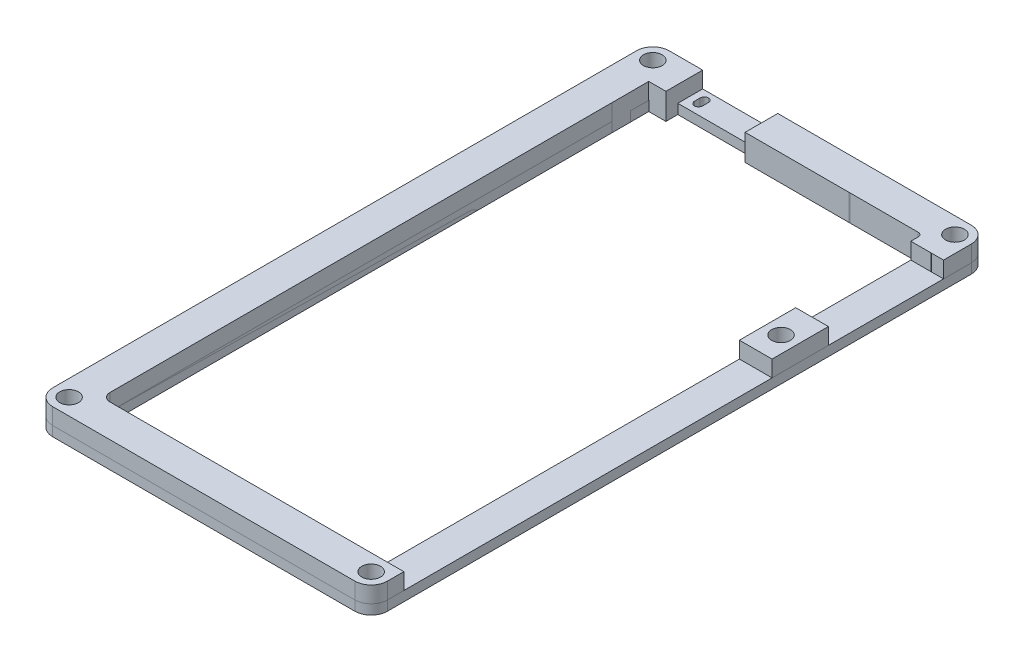
SolidWorks part; units mm, degrees
ref_plane "Front Plane" through (0, 0, 0) normal (0, 0, 1) x (1, 0, 0)
ref_plane "Top Plane" through (0, 0, 0) normal (0, 1, 0) x (1, 0, 0)
ref_plane "Right Plane" through (0, 0, 0) normal (1, 0, 0) x (0, 0, -1)
sketch "partA" plane through (0, 0, 0) normal (0, 1, 0) x (1, 0, 0)
  line L0 (1, 63.5) -> (19.3, 63.5)
  line L1 (19.3, 63.5) -> (22.7142, 66.9142)
  line L2 (0, 62.5) -> (0, 1)
  line L3 (33, 66.1) -> (33, 67)
  line L4 (32.5, 67.5) -> (24.1284, 67.5)
  line L5 (1, 0) -> (37, 0)
  line L6 (-4, -2) -> (-4, 69.5)
  line L7 (-2, 71.5) -> (2.1, 71.5)
  line L8 (37, 0) -> (37, -2)
  line L9 (35, -4) -> (-2, -4)
  line L10 (2.1, 71.5) -> (2.1, 67)
  line L11 (2.6, 66.5) -> (10.8, 66.5)
  line L12 (11.3, 67) -> (11.3, 71.5)
  line L13 (37, 66.1) -> (35.5, 66.1)
  line L14 (35, 65.6) -> (35, 52.5)
  line L15 (35.5, 52) -> (37, 52)
  line L16 (11.3, 71.5) -> (35, 71.5)
  line L17 (37, 69.5) -> (37, 66.1)
  line L18 (37, 45.1) -> (37, 52)
  line L19 (33, 45.1) -> (33, 52)
  line L20 (33, 45.1) -> (37, 45.1)
  line L21 (33, 66.1) -> (33, 52)
  line L22 (37, 52) -> (33, 52)
  line L23 (37, 66.1) -> (33, 66.1)
  arc A0 (19.3, 63.4975) -> (19.3, 63.5025) centre (19.3, 63.5) ccw
  arc A1 (1, 63.5025) -> (1, 63.4975) centre (1, 63.5) ccw
  arc A2 (22.716, 66.9124) -> (22.7124, 66.916) centre (22.7142, 66.9142) ccw
  arc A3 (19.2982, 63.5018) -> (19.3018, 63.4982) centre (19.3, 63.5) ccw
  arc A4 (1, 63.5) -> (0, 62.5) centre (1, 62.5) ccw
  arc A5 (1, 63.4975) -> (1, 63.5025) centre (1, 63.5) ccw
  arc A6 (-0.0025, 62.5) -> (0.0025, 62.5) centre (0, 62.5) ccw
  arc A7 (-0.0025, 1) -> (0.0025, 1) centre (0, 1) ccw
  arc A8 (0.0025, 62.5) -> (-0.0025, 62.5) centre (0, 62.5) ccw
  arc A9 (24.1284, 67.5) -> (22.7142, 66.9142) centre (24.1285, 65.4999) ccw
  arc A10 (24.1284, 67.4975) -> (24.1284, 67.5025) centre (24.1284, 67.5) ccw
  arc A11 (22.7124, 66.916) -> (22.716, 66.9124) centre (22.7142, 66.9142) ccw
  arc A12 (33.0025, 67) -> (32.9975, 67) centre (33, 67) ccw
  arc A13 (32.9975, 66.1) -> (33.0025, 66.1) centre (33, 66.1) ccw
  arc A14 (33, 67) -> (32.5, 67.5) centre (32.5, 67) ccw
  arc A15 (32.9975, 67) -> (33.0025, 67) centre (33, 67) ccw
  arc A16 (32.5, 67.5025) -> (32.5, 67.4975) centre (32.5, 67.5) ccw
  arc A17 (24.1284, 67.5025) -> (24.1284, 67.4975) centre (24.1284, 67.5) ccw
  arc A18 (32.5, 67.4975) -> (32.5, 67.5025) centre (32.5, 67.5) ccw
  arc A19 (0, 1) -> (1, 0) centre (1, 1) ccw
  arc A20 (0.0025, 1) -> (-0.0025, 1) centre (0, 1) ccw
  arc A21 (1, -0.0025) -> (1, 0.0025) centre (1, 0) ccw
  arc A22 (37, -0.0025) -> (37, 0.0025) centre (37, 0) ccw
  arc A23 (1, 0.0025) -> (1, -0.0025) centre (1, 0) ccw
  arc A24 (-3.9975, 69.5) -> (-4.0025, 69.5) centre (-4, 69.5) ccw
  arc A25 (-4.0025, -2) -> (-3.9975, -2) centre (-4, -2) ccw
  arc A26 (-2, 71.5) -> (-4, 69.5) centre (-2, 69.5) ccw
  arc A27 (-2, 71.4975) -> (-2, 71.5025) centre (-2, 71.5) ccw
  arc A28 (-4.0025, 69.5) -> (-3.9975, 69.5) centre (-4, 69.5) ccw
  arc A29 (2.1, 71.4975) -> (2.1, 71.5025) centre (2.1, 71.5) ccw
  arc A30 (-2, 71.5025) -> (-2, 71.4975) centre (-2, 71.5) ccw
  arc A31 (36.9975, -2) -> (37.0025, -2) centre (37, -2) ccw
  arc A32 (37.0025, 0) -> (36.9975, 0) centre (37, 0) ccw
  arc A33 (35, -4) -> (37, -2) centre (35, -2) ccw
  arc A34 (35, -3.9975) -> (35, -4.0025) centre (35, -4) ccw
  arc A35 (37.0025, -2) -> (36.9975, -2) centre (37, -2) ccw
  arc A36 (-2, -3.9975) -> (-2, -4.0025) centre (-2, -4) ccw
  arc A37 (35, -4.0025) -> (35, -3.9975) centre (35, -4) ccw
  arc A38 (-4, -2) -> (-2, -4) centre (-2, -2) ccw
  arc A39 (-3.9975, -2) -> (-4.0025, -2) centre (-4, -2) ccw
  arc A40 (-2, -4.0025) -> (-2, -3.9975) centre (-2, -4) ccw
  arc A41 (2.0975, 67) -> (2.1025, 67) centre (2.1, 67) ccw
  arc A42 (2.1025, 71.5) -> (2.0975, 71.5) centre (2.1, 71.5) ccw
  arc A43 (2.1, 67) -> (2.6, 66.5) centre (2.6, 67) ccw
  arc A44 (2.1025, 67) -> (2.0975, 67) centre (2.1, 67) ccw
  arc A45 (2.6, 66.4975) -> (2.6, 66.5025) centre (2.6, 66.5) ccw
  arc A46 (10.8, 66.4975) -> (10.8, 66.5025) centre (10.8, 66.5) ccw
  arc A47 (2.6, 66.5025) -> (2.6, 66.4975) centre (2.6, 66.5) ccw
  arc A48 (10.8, 66.5) -> (11.3, 67) centre (10.8, 67) ccw
  arc A49 (10.8, 66.5025) -> (10.8, 66.4975) centre (10.8, 66.5) ccw
  arc A50 (11.3025, 67) -> (11.2975, 67) centre (11.3, 67) ccw
  arc A51 (11.3025, 71.5) -> (11.2975, 71.5) centre (11.3, 71.5) ccw
  arc A52 (11.2975, 67) -> (11.3025, 67) centre (11.3, 67) ccw
  arc A53 (35.5, 66.1025) -> (35.5, 66.0975) centre (35.5, 66.1) ccw
  arc A54 (37, 66.0975) -> (37, 66.1025) centre (37, 66.1) ccw
  arc A55 (35.5, 66.1) -> (35, 65.6) centre (35.5, 65.6) ccw
  arc A56 (35.5, 66.0975) -> (35.5, 66.1025) centre (35.5, 66.1) ccw
  arc A57 (34.9975, 65.6) -> (35.0025, 65.6) centre (35, 65.6) ccw
  arc A58 (34.9975, 52.5) -> (35.0025, 52.5) centre (35, 52.5) ccw
  arc A59 (35.0025, 65.6) -> (34.9975, 65.6) centre (35, 65.6) ccw
  arc A60 (35, 52.5) -> (35.5, 52) centre (35.5, 52.5) ccw
  arc A61 (35.0025, 52.5) -> (34.9975, 52.5) centre (35, 52.5) ccw
  arc A62 (35.5, 51.9975) -> (35.5, 52.0025) centre (35.5, 52) ccw
  arc A63 (37, 51.9975) -> (37, 52.0025) centre (37, 52) ccw
  arc A64 (35.5, 52.0025) -> (35.5, 51.9975) centre (35.5, 52) ccw
  arc A65 (35, 71.4975) -> (35, 71.5025) centre (35, 71.5) ccw
  arc A66 (11.3, 71.5025) -> (11.3, 71.4975) centre (11.3, 71.5) ccw
  arc A67 (37, 69.5) -> (35, 71.5) centre (35, 69.5) ccw
  arc A68 (36.9975, 69.5) -> (37.0025, 69.5) centre (37, 69.5) ccw
  arc A69 (35, 71.5025) -> (35, 71.4975) centre (35, 71.5) ccw
  arc A70 (36.9975, 66.1) -> (37.0025, 66.1) centre (37, 66.1) ccw
  arc A71 (37.0025, 69.5) -> (36.9975, 69.5) centre (37, 69.5) ccw
  arc A72 (37.0025, 52) -> (36.9975, 52) centre (37, 52) ccw
  arc A73 (36.9975, 45.1) -> (37.0025, 45.1) centre (37, 45.1) ccw
  arc A74 (33.0025, 52) -> (32.9975, 52) centre (33, 52) ccw
  arc A75 (32.9975, 45.1) -> (33.0025, 45.1) centre (33, 45.1) ccw
  arc A76 (37, 45.0975) -> (37, 45.1025) centre (37, 45.1) ccw
  arc A77 (33, 45.1025) -> (33, 45.0975) centre (33, 45.1) ccw
  arc A78 (32.9975, 52) -> (33.0025, 52) centre (33, 52) ccw
  arc A79 (33.0025, 66.1) -> (32.9975, 66.1) centre (33, 66.1) ccw
  arc A80 (33, 52.0025) -> (33, 51.9975) centre (33, 52) ccw
  arc A81 (37, 51.9975) -> (37, 52.0025) centre (37, 52) ccw
  arc A82 (33, 66.1025) -> (33, 66.0975) centre (33, 66.1) ccw
  arc A83 (37, 66.0975) -> (37, 66.1025) centre (37, 66.1) ccw
  circle A84 centre (-2, 69.5) radius 1
  circle A85 centre (35, 69.5) radius 1
  circle A86 centre (35, -2) radius 1
  circle A87 centre (-2, -2) radius 1
  circle A88 centre (35, 48.2) radius 1
  circle A89 centre (33.3, 51.7) radius 0.3
  circle A90 centre (34.1, 51.7) radius 0.3
  circle A91 centre (34.9, 51.7) radius 0.3
  circle A92 centre (35.7, 51.7) radius 0.3
  circle A93 centre (33.3, 66.4) radius 0.3
  circle A94 centre (34.1, 66.4) radius 0.3
  circle A95 centre (34.9, 66.4) radius 0.3
  circle A96 centre (35.7, 66.4) radius 0.3
sketch "partC" plane through (0, 0, 0) normal (0, 1, 0) x (1, 0, 0)
  line L0 (-4, -2) -> (-4, 69.5)
  line L1 (-2, 71.5) -> (35, 71.5)
  line L2 (37, 69.5) -> (37, -2)
  line L3 (35, -4) -> (-2, -4)
  line L4 (-4, -2) -> (-4, 69.5)
  line L5 (-2, 71.5) -> (35, 71.5)
  line L6 (37, 69.5) -> (37, -2)
  line L7 (35, -4) -> (-2, -4)
  line L8 (2.9, 69.7) -> (2.9, 70.4)
  line L9 (3.9, 70.4) -> (3.9, 69.7)
  line L10 (9.5, 69.7) -> (9.5, 70.4)
  line L11 (10.5, 70.4) -> (10.5, 69.7)
  line L12 (29, 68) -> (23.5, 68)
  line L13 (23, 67.5) -> (23, 50.5)
  line L14 (23.5, 50) -> (29, 50)
  line L15 (29.5, 50.5) -> (29.5, 67.5)
  line L16 (20.7, 1.7) -> (20.7, 2.6)
  line L17 (21.2, 3.1) -> (29.8, 3.1)
  line L18 (30.3, 2.6) -> (30.3, 1.7)
  line L19 (29.8, 1.2) -> (21.2, 1.2)
  line L20 (12.6, 15.2) -> (12.6, 16.1)
  line L21 (13.1, 16.6) -> (21.7, 16.6)
  line L22 (22.2, 16.1) -> (22.2, 15.2)
  line L23 (21.7, 14.7) -> (13.1, 14.7)
  line L24 (20.7, 19.7) -> (20.7, 20.6)
  line L25 (21.2, 21.1) -> (29.8, 21.1)
  line L26 (30.3, 20.6) -> (30.3, 19.7)
  line L27 (29.8, 19.2) -> (21.2, 19.2)
  line L28 (12.6, 33.2) -> (12.6, 34.1)
  line L29 (13.1, 34.6) -> (21.7, 34.6)
  line L30 (22.2, 34.1) -> (22.2, 33.2)
  line L31 (21.7, 32.7) -> (13.1, 32.7)
  arc A0 (-3.9975, 69.5) -> (-4.0025, 69.5) centre (-4, 69.5) ccw
  arc A1 (-4.0025, -2) -> (-3.9975, -2) centre (-4, -2) ccw
  arc A2 (-2, 71.5) -> (-4, 69.5) centre (-2, 69.5) ccw
  arc A3 (-2, 71.4975) -> (-2, 71.5025) centre (-2, 71.5) ccw
  arc A4 (-4.0025, 69.5) -> (-3.9975, 69.5) centre (-4, 69.5) ccw
  arc A5 (35, 71.4975) -> (35, 71.5025) centre (35, 71.5) ccw
  arc A6 (-2, 71.5025) -> (-2, 71.4975) centre (-2, 71.5) ccw
  arc A7 (-4, -2) -> (-2, -4) centre (-2, -2) ccw
  arc A8 (-3.9975, -2) -> (-4.0025, -2) centre (-4, -2) ccw
  arc A9 (-2, -4.0025) -> (-2, -3.9975) centre (-2, -4) ccw
  arc A10 (37, 69.5) -> (35, 71.5) centre (35, 69.5) ccw
  arc A11 (36.9975, 69.5) -> (37.0025, 69.5) centre (37, 69.5) ccw
  arc A12 (35, 71.5025) -> (35, 71.4975) centre (35, 71.5) ccw
  arc A13 (36.9975, -2) -> (37.0025, -2) centre (37, -2) ccw
  arc A14 (37.0025, 69.5) -> (36.9975, 69.5) centre (37, 69.5) ccw
  arc A15 (35, -4) -> (37, -2) centre (35, -2) ccw
  arc A16 (35, -3.9975) -> (35, -4.0025) centre (35, -4) ccw
  arc A17 (37.0025, -2) -> (36.9975, -2) centre (37, -2) ccw
  arc A18 (-2, -3.9975) -> (-2, -4.0025) centre (-2, -4) ccw
  arc A19 (35, -4.0025) -> (35, -3.9975) centre (35, -4) ccw
  arc A20 (-3.9975, 69.5) -> (-4.0025, 69.5) centre (-4, 69.5) ccw
  arc A21 (-4.0025, -2) -> (-3.9975, -2) centre (-4, -2) ccw
  arc A22 (-2, 71.5) -> (-4, 69.5) centre (-2, 69.5) ccw
  arc A23 (-2, 71.4975) -> (-2, 71.5025) centre (-2, 71.5) ccw
  arc A24 (-4.0025, 69.5) -> (-3.9975, 69.5) centre (-4, 69.5) ccw
  arc A25 (35, 71.4975) -> (35, 71.5025) centre (35, 71.5) ccw
  arc A26 (-2, 71.5025) -> (-2, 71.4975) centre (-2, 71.5) ccw
  arc A27 (-4, -2) -> (-2, -4) centre (-2, -2) ccw
  arc A28 (-3.9975, -2) -> (-4.0025, -2) centre (-4, -2) ccw
  arc A29 (-2, -4.0025) -> (-2, -3.9975) centre (-2, -4) ccw
  arc A30 (37, 69.5) -> (35, 71.5) centre (35, 69.5) ccw
  arc A31 (36.9975, 69.5) -> (37.0025, 69.5) centre (37, 69.5) ccw
  arc A32 (35, 71.5025) -> (35, 71.4975) centre (35, 71.5) ccw
  arc A33 (36.9975, -2) -> (37.0025, -2) centre (37, -2) ccw
  arc A34 (37.0025, 69.5) -> (36.9975, 69.5) centre (37, 69.5) ccw
  arc A35 (35, -4) -> (37, -2) centre (35, -2) ccw
  arc A36 (35, -3.9975) -> (35, -4.0025) centre (35, -4) ccw
  arc A37 (37.0025, -2) -> (36.9975, -2) centre (37, -2) ccw
  arc A38 (-2, -3.9975) -> (-2, -4.0025) centre (-2, -4) ccw
  arc A39 (35, -4.0025) -> (35, -3.9975) centre (35, -4) ccw
  arc A40 (2.9025, 70.4) -> (2.8975, 70.4) centre (2.9, 70.4) ccw
  arc A41 (2.8975, 69.7) -> (2.9025, 69.7) centre (2.9, 69.7) ccw
  arc A42 (3.4, 70.9) -> (2.9, 70.4) centre (3.4, 70.4) ccw
  arc A43 (3.4, 70.8975) -> (3.4, 70.9025) centre (3.4, 70.9) ccw
  arc A44 (2.8975, 70.4) -> (2.9025, 70.4) centre (2.9, 70.4) ccw
  arc A45 (3.9, 70.4) -> (3.4, 70.9) centre (3.4, 70.4) ccw
  arc A46 (3.8975, 70.4) -> (3.9025, 70.4) centre (3.9, 70.4) ccw
  arc A47 (3.4, 70.9025) -> (3.4, 70.8975) centre (3.4, 70.9) ccw
  arc A48 (3.8975, 69.7) -> (3.9025, 69.7) centre (3.9, 69.7) ccw
  arc A49 (3.9025, 70.4) -> (3.8975, 70.4) centre (3.9, 70.4) ccw
  arc A50 (3.4, 69.2) -> (3.9, 69.7) centre (3.4, 69.7) ccw
  arc A51 (3.4, 69.2025) -> (3.4, 69.1975) centre (3.4, 69.2) ccw
  arc A52 (3.9025, 69.7) -> (3.8975, 69.7) centre (3.9, 69.7) ccw
  arc A53 (2.9, 69.7) -> (3.4, 69.2) centre (3.4, 69.7) ccw
  arc A54 (2.9025, 69.7) -> (2.8975, 69.7) centre (2.9, 69.7) ccw
  arc A55 (3.4, 69.1975) -> (3.4, 69.2025) centre (3.4, 69.2) ccw
  arc A56 (9.5025, 70.4) -> (9.4975, 70.4) centre (9.5, 70.4) ccw
  arc A57 (9.4975, 69.7) -> (9.5025, 69.7) centre (9.5, 69.7) ccw
  arc A58 (10, 70.9) -> (9.5, 70.4) centre (10, 70.4) ccw
  arc A59 (10, 70.8975) -> (10, 70.9025) centre (10, 70.9) ccw
  arc A60 (9.4975, 70.4) -> (9.5025, 70.4) centre (9.5, 70.4) ccw
  arc A61 (10.5, 70.4) -> (10, 70.9) centre (10, 70.4) ccw
  arc A62 (10.4975, 70.4) -> (10.5025, 70.4) centre (10.5, 70.4) ccw
  arc A63 (10, 70.9025) -> (10, 70.8975) centre (10, 70.9) ccw
  arc A64 (10.4975, 69.7) -> (10.5025, 69.7) centre (10.5, 69.7) ccw
  arc A65 (10.5025, 70.4) -> (10.4975, 70.4) centre (10.5, 70.4) ccw
  arc A66 (10, 69.2) -> (10.5, 69.7) centre (10, 69.7) ccw
  arc A67 (10, 69.2025) -> (10, 69.1975) centre (10, 69.2) ccw
  arc A68 (10.5025, 69.7) -> (10.4975, 69.7) centre (10.5, 69.7) ccw
  arc A69 (9.5, 69.7) -> (10, 69.2) centre (10, 69.7) ccw
  arc A70 (9.5025, 69.7) -> (9.4975, 69.7) centre (9.5, 69.7) ccw
  arc A71 (10, 69.1975) -> (10, 69.2025) centre (10, 69.2) ccw
  arc A72 (23.5, 68.0025) -> (23.5, 67.9975) centre (23.5, 68) ccw
  arc A73 (29, 67.9975) -> (29, 68.0025) centre (29, 68) ccw
  arc A74 (23.5, 68) -> (23, 67.5) centre (23.5, 67.5) ccw
  arc A75 (23.5, 67.9975) -> (23.5, 68.0025) centre (23.5, 68) ccw
  arc A76 (22.9975, 67.5) -> (23.0025, 67.5) centre (23, 67.5) ccw
  arc A77 (22.9975, 50.5) -> (23.0025, 50.5) centre (23, 50.5) ccw
  arc A78 (23.0025, 67.5) -> (22.9975, 67.5) centre (23, 67.5) ccw
  arc A79 (23, 50.5) -> (23.5, 50) centre (23.5, 50.5) ccw
  arc A80 (23.0025, 50.5) -> (22.9975, 50.5) centre (23, 50.5) ccw
  arc A81 (23.5, 49.9975) -> (23.5, 50.0025) centre (23.5, 50) ccw
  arc A82 (29, 49.9975) -> (29, 50.0025) centre (29, 50) ccw
  arc A83 (23.5, 50.0025) -> (23.5, 49.9975) centre (23.5, 50) ccw
  arc A84 (29, 50) -> (29.5, 50.5) centre (29, 50.5) ccw
  arc A85 (29, 50.0025) -> (29, 49.9975) centre (29, 50) ccw
  arc A86 (29.5025, 50.5) -> (29.4975, 50.5) centre (29.5, 50.5) ccw
  arc A87 (29.5025, 67.5) -> (29.4975, 67.5) centre (29.5, 67.5) ccw
  arc A88 (29.4975, 50.5) -> (29.5025, 50.5) centre (29.5, 50.5) ccw
  arc A89 (29.5, 67.5) -> (29, 68) centre (29, 67.5) ccw
  arc A90 (29.4975, 67.5) -> (29.5025, 67.5) centre (29.5, 67.5) ccw
  arc A91 (29, 68.0025) -> (29, 67.9975) centre (29, 68) ccw
  arc A92 (20.7025, 2.6) -> (20.6975, 2.6) centre (20.7, 2.6) ccw
  arc A93 (20.6975, 1.7) -> (20.7025, 1.7) centre (20.7, 1.7) ccw
  arc A94 (21.2, 3.1) -> (20.7, 2.6) centre (21.2, 2.6) ccw
  arc A95 (21.2, 3.0975) -> (21.2, 3.1025) centre (21.2, 3.1) ccw
  arc A96 (20.6975, 2.6) -> (20.7025, 2.6) centre (20.7, 2.6) ccw
  arc A97 (29.8, 3.0975) -> (29.8, 3.1025) centre (29.8, 3.1) ccw
  arc A98 (21.2, 3.1025) -> (21.2, 3.0975) centre (21.2, 3.1) ccw
  arc A99 (30.3, 2.6) -> (29.8, 3.1) centre (29.8, 2.6) ccw
  arc A100 (30.2975, 2.6) -> (30.3025, 2.6) centre (30.3, 2.6) ccw
  arc A101 (29.8, 3.1025) -> (29.8, 3.0975) centre (29.8, 3.1) ccw
  arc A102 (30.2975, 1.7) -> (30.3025, 1.7) centre (30.3, 1.7) ccw
  arc A103 (30.3025, 2.6) -> (30.2975, 2.6) centre (30.3, 2.6) ccw
  arc A104 (29.8, 1.2) -> (30.3, 1.7) centre (29.8, 1.7) ccw
  arc A105 (29.8, 1.2025) -> (29.8, 1.1975) centre (29.8, 1.2) ccw
  arc A106 (30.3025, 1.7) -> (30.2975, 1.7) centre (30.3, 1.7) ccw
  arc A107 (21.2, 1.2025) -> (21.2, 1.1975) centre (21.2, 1.2) ccw
  arc A108 (29.8, 1.1975) -> (29.8, 1.2025) centre (29.8, 1.2) ccw
  arc A109 (20.7, 1.7) -> (21.2, 1.2) centre (21.2, 1.7) ccw
  arc A110 (20.7025, 1.7) -> (20.6975, 1.7) centre (20.7, 1.7) ccw
  arc A111 (21.2, 1.1975) -> (21.2, 1.2025) centre (21.2, 1.2) ccw
  arc A112 (12.6025, 16.1) -> (12.5975, 16.1) centre (12.6, 16.1) ccw
  arc A113 (12.5975, 15.2) -> (12.6025, 15.2) centre (12.6, 15.2) ccw
  arc A114 (13.1, 16.6) -> (12.6, 16.1) centre (13.1, 16.1) ccw
  arc A115 (13.1, 16.5975) -> (13.1, 16.6025) centre (13.1, 16.6) ccw
  arc A116 (12.5975, 16.1) -> (12.6025, 16.1) centre (12.6, 16.1) ccw
  arc A117 (21.7, 16.5975) -> (21.7, 16.6025) centre (21.7, 16.6) ccw
  arc A118 (13.1, 16.6025) -> (13.1, 16.5975) centre (13.1, 16.6) ccw
  arc A119 (22.2, 16.1) -> (21.7, 16.6) centre (21.7, 16.1) ccw
  arc A120 (22.1975, 16.1) -> (22.2025, 16.1) centre (22.2, 16.1) ccw
  arc A121 (21.7, 16.6025) -> (21.7, 16.5975) centre (21.7, 16.6) ccw
  arc A122 (22.1975, 15.2) -> (22.2025, 15.2) centre (22.2, 15.2) ccw
  arc A123 (22.2025, 16.1) -> (22.1975, 16.1) centre (22.2, 16.1) ccw
  arc A124 (21.7, 14.7) -> (22.2, 15.2) centre (21.7, 15.2) ccw
  arc A125 (21.7, 14.7025) -> (21.7, 14.6975) centre (21.7, 14.7) ccw
  arc A126 (22.2025, 15.2) -> (22.1975, 15.2) centre (22.2, 15.2) ccw
  arc A127 (13.1, 14.7025) -> (13.1, 14.6975) centre (13.1, 14.7) ccw
  arc A128 (21.7, 14.6975) -> (21.7, 14.7025) centre (21.7, 14.7) ccw
  arc A129 (12.6, 15.2) -> (13.1, 14.7) centre (13.1, 15.2) ccw
  arc A130 (12.6025, 15.2) -> (12.5975, 15.2) centre (12.6, 15.2) ccw
  arc A131 (13.1, 14.6975) -> (13.1, 14.7025) centre (13.1, 14.7) ccw
  arc A132 (20.7025, 20.6) -> (20.6975, 20.6) centre (20.7, 20.6) ccw
  arc A133 (20.6975, 19.7) -> (20.7025, 19.7) centre (20.7, 19.7) ccw
  arc A134 (21.2, 21.1) -> (20.7, 20.6) centre (21.2, 20.6) ccw
  arc A135 (21.2, 21.0975) -> (21.2, 21.1025) centre (21.2, 21.1) ccw
  arc A136 (20.6975, 20.6) -> (20.7025, 20.6) centre (20.7, 20.6) ccw
  arc A137 (29.8, 21.0975) -> (29.8, 21.1025) centre (29.8, 21.1) ccw
  arc A138 (21.2, 21.1025) -> (21.2, 21.0975) centre (21.2, 21.1) ccw
  arc A139 (30.3, 20.6) -> (29.8, 21.1) centre (29.8, 20.6) ccw
  arc A140 (30.2975, 20.6) -> (30.3025, 20.6) centre (30.3, 20.6) ccw
  arc A141 (29.8, 21.1025) -> (29.8, 21.0975) centre (29.8, 21.1) ccw
  arc A142 (30.2975, 19.7) -> (30.3025, 19.7) centre (30.3, 19.7) ccw
  arc A143 (30.3025, 20.6) -> (30.2975, 20.6) centre (30.3, 20.6) ccw
  arc A144 (29.8, 19.2) -> (30.3, 19.7) centre (29.8, 19.7) ccw
  arc A145 (29.8, 19.2025) -> (29.8, 19.1975) centre (29.8, 19.2) ccw
  arc A146 (30.3025, 19.7) -> (30.2975, 19.7) centre (30.3, 19.7) ccw
  arc A147 (21.2, 19.2025) -> (21.2, 19.1975) centre (21.2, 19.2) ccw
  arc A148 (29.8, 19.1975) -> (29.8, 19.2025) centre (29.8, 19.2) ccw
  arc A149 (20.7, 19.7) -> (21.2, 19.2) centre (21.2, 19.7) ccw
  arc A150 (20.7025, 19.7) -> (20.6975, 19.7) centre (20.7, 19.7) ccw
  arc A151 (21.2, 19.1975) -> (21.2, 19.2025) centre (21.2, 19.2) ccw
  arc A152 (12.6025, 34.1) -> (12.5975, 34.1) centre (12.6, 34.1) ccw
  arc A153 (12.5975, 33.2) -> (12.6025, 33.2) centre (12.6, 33.2) ccw
  arc A154 (13.1, 34.6) -> (12.6, 34.1) centre (13.1, 34.1) ccw
  arc A155 (13.1, 34.5975) -> (13.1, 34.6025) centre (13.1, 34.6) ccw
  arc A156 (12.5975, 34.1) -> (12.6025, 34.1) centre (12.6, 34.1) ccw
  arc A157 (21.7, 34.5975) -> (21.7, 34.6025) centre (21.7, 34.6) ccw
  arc A158 (13.1, 34.6025) -> (13.1, 34.5975) centre (13.1, 34.6) ccw
  arc A159 (22.2, 34.1) -> (21.7, 34.6) centre (21.7, 34.1) ccw
  arc A160 (22.1975, 34.1) -> (22.2025, 34.1) centre (22.2, 34.1) ccw
  arc A161 (21.7, 34.6025) -> (21.7, 34.5975) centre (21.7, 34.6) ccw
  arc A162 (22.1975, 33.2) -> (22.2025, 33.2) centre (22.2, 33.2) ccw
  arc A163 (22.2025, 34.1) -> (22.1975, 34.1) centre (22.2, 34.1) ccw
  arc A164 (21.7, 32.7) -> (22.2, 33.2) centre (21.7, 33.2) ccw
  arc A165 (21.7, 32.7025) -> (21.7, 32.6975) centre (21.7, 32.7) ccw
  arc A166 (22.2025, 33.2) -> (22.1975, 33.2) centre (22.2, 33.2) ccw
  arc A167 (13.1, 32.7025) -> (13.1, 32.6975) centre (13.1, 32.7) ccw
  arc A168 (21.7, 32.6975) -> (21.7, 32.7025) centre (21.7, 32.7) ccw
  arc A169 (12.6, 33.2) -> (13.1, 32.7) centre (13.1, 33.2) ccw
  arc A170 (12.6025, 33.2) -> (12.5975, 33.2) centre (12.6, 33.2) ccw
  arc A171 (13.1, 32.6975) -> (13.1, 32.7025) centre (13.1, 32.7) ccw
  circle A172 centre (-2, 69.5) radius 1
  circle A173 centre (35, 69.5) radius 1
  circle A174 centre (35, -2) radius 1
  circle A175 centre (-2, -2) radius 1
  circle A176 centre (35, 48.2) radius 1
sketch "A-modify" plane through (0, 0, 0) normal (0, 1, 0) x (1, 0, 0)
  line L0 (1, 63.5) -> (1.0025, 63.5)
  line L1 (35, 52.5025) -> (35, 52.5)
  line L2 (0, 62.5) -> (0, 1)
  line L3 (33, 66.1) -> (33, 67)
  line L4 (32.5, 67.5) -> (24.1284, 67.5)
  line L5 (1, 0) -> (37, 0)
  line L6 (-4, -2) -> (-4, 69.5)
  line L7 (-2, 71.5) -> (2.1, 71.5)
  line L8 (37, 0) -> (37, -2)
  line L9 (35, -4) -> (-2, -4)
  line L10 (2.1, 71.5) -> (2.1, 67)
  line L11 (2.6, 66.5) -> (2.6025, 66.5)
  line L12 (11.3, 67) -> (11.3, 67.0025)
  line L13 (37, 66.1) -> (35.5, 66.1)
  line L14 (35, 65.6) -> (35, 65.5975)
  line L15 (35.5, 52) -> (37, 52)
  line L16 (11.3, 71.5) -> (35, 71.5)
  line L17 (37, 69.5) -> (37, 66.1)
  line L18 (37, 45.1) -> (37, 52)
  line L19 (33, 45.1) -> (33, 52)
  line L20 (33, 45.1) -> (37, 45.1)
  line L21 (33, 66.1) -> (33, 66.0975)
  line L22 (37, 52) -> (35.4975, 52)
  line L23 (37, 66.1) -> (35.4975, 66.1)
  line L24 (-0.0025, 67) -> (0.0025, 62.5)
  line L25 (19.2975, 63.5) -> (19.3, 63.5)
  line L27 (24.1284, 67.4975) -> (11.3, 67.4975)
  line L28 (33, 52.0025) -> (33, 52)
  line L29 (33.0025, 52) -> (33, 52)
  line L30 (33, 51.9975) -> (35.5, 51.9975)
  line L31 (33.0025, 66.1) -> (33, 66.1)
  line L32 (35.5, 66.0975) -> (33, 66.0975)
  line L33 (10.7975, 66.5) -> (10.8, 66.5)
  line L34 (11.3, 67.4975) -> (11.3, 71.5)
  line L35 (2.0975, 67) -> (-0.0025, 67)
  arc A0 (19.3, 63.4975) -> (19.3, 63.5025) centre (19.3, 63.5) ccw
  arc A1 (1, 63.5025) -> (1, 63.4975) centre (1, 63.5) ccw
  arc A2 (22.716, 66.9124) -> (22.7124, 66.916) centre (22.7142, 66.9142) ccw
  arc A3 (19.2982, 63.5018) -> (19.3018, 63.4982) centre (19.3, 63.5) ccw
  arc A4 (1, 63.5) -> (0.9975, 63.5) centre (1, 62.5) ccw
  arc A5 (1, 63.4975) -> (1, 63.5025) centre (1, 63.5) ccw
  arc A6 (-0.0025, 62.5) -> (0.0025, 62.5) centre (0, 62.5) ccw
  arc A7 (-0.0025, 1) -> (0.0025, 1) centre (0, 1) ccw
  arc A8 (0.0025, 62.5) -> (-0.0025, 62.5) centre (0, 62.5) ccw
  arc A9 (24.1284, 67.5) -> (24.0285, 67.4975) centre (24.1285, 65.4999) ccw
  arc A10 (24.1284, 67.4975) -> (24.1284, 67.5025) centre (24.1284, 67.5) ccw
  arc A11 (22.7124, 66.916) -> (22.716, 66.9124) centre (22.7142, 66.9142) ccw
  arc A12 (33.0025, 67) -> (32.9975, 67) centre (33, 67) ccw
  arc A13 (32.9975, 66.1) -> (33.0025, 66.1) centre (33, 66.1) ccw
  arc A14 (33, 67) -> (32.5, 67.5) centre (32.5, 67) ccw
  arc A15 (32.9975, 67) -> (33.0025, 67) centre (33, 67) ccw
  arc A16 (32.5, 67.5025) -> (32.5, 67.4975) centre (32.5, 67.5) ccw
  arc A17 (24.1284, 67.5025) -> (24.1284, 67.4975) centre (24.1284, 67.5) ccw
  arc A18 (32.5, 67.4975) -> (32.5, 67.5025) centre (32.5, 67.5) ccw
  arc A19 (0, 1) -> (1, 0) centre (1, 1) ccw
  arc A20 (0.0025, 1) -> (-0.0025, 1) centre (0, 1) ccw
  arc A21 (1, -0.0025) -> (1, 0.0025) centre (1, 0) ccw
  arc A22 (37, -0.0025) -> (37, 0.0025) centre (37, 0) ccw
  arc A23 (1, 0.0025) -> (1, -0.0025) centre (1, 0) ccw
  arc A24 (-3.9975, 69.5) -> (-4.0025, 69.5) centre (-4, 69.5) ccw
  arc A25 (-4.0025, -2) -> (-3.9975, -2) centre (-4, -2) ccw
  arc A26 (-2, 71.5) -> (-4, 69.5) centre (-2, 69.5) ccw
  arc A27 (-2, 71.4975) -> (-2, 71.5025) centre (-2, 71.5) ccw
  arc A28 (-4.0025, 69.5) -> (-3.9975, 69.5) centre (-4, 69.5) ccw
  arc A29 (2.1, 71.4975) -> (2.1, 71.5025) centre (2.1, 71.5) ccw
  arc A30 (-2, 71.5025) -> (-2, 71.4975) centre (-2, 71.5) ccw
  arc A31 (36.9975, -2) -> (37.0025, -2) centre (37, -2) ccw
  arc A32 (37.0025, 0) -> (36.9975, 0) centre (37, 0) ccw
  arc A33 (35, -4) -> (37, -2) centre (35, -2) ccw
  arc A34 (35, -3.9975) -> (35, -4.0025) centre (35, -4) ccw
  arc A35 (37.0025, -2) -> (36.9975, -2) centre (37, -2) ccw
  arc A36 (-2, -3.9975) -> (-2, -4.0025) centre (-2, -4) ccw
  arc A37 (35, -4.0025) -> (35, -3.9975) centre (35, -4) ccw
  arc A38 (-4, -2) -> (-2, -4) centre (-2, -2) ccw
  arc A39 (-3.9975, -2) -> (-4.0025, -2) centre (-4, -2) ccw
  arc A40 (-2, -4.0025) -> (-2, -3.9975) centre (-2, -4) ccw
  arc A41 (2.0975, 67) -> (2.1025, 67) centre (2.1, 67) ccw
  arc A42 (2.1025, 71.5) -> (2.0975, 71.5) centre (2.1, 71.5) ccw
  circle A43 centre (-2, -2) radius 1.15
  arc A44 (2.1025, 67) -> (2.0975, 67) centre (2.1, 67) ccw
  arc A45 (2.6, 66.4975) -> (2.6, 66.5025) centre (2.6, 66.5) ccw
  arc A46 (10.8, 66.4975) -> (10.8, 66.5025) centre (10.8, 66.5) ccw
  arc A47 (2.6, 66.5025) -> (2.6, 66.4975) centre (2.6, 66.5) ccw
  arc A48 (10.8, 66.5) -> (10.8025, 66.5) centre (10.8, 67) ccw
  arc A49 (10.8, 66.5025) -> (10.8, 66.4975) centre (10.8, 66.5) ccw
  arc A50 (11.3025, 67) -> (11.2975, 67) centre (11.3, 67) ccw
  arc A51 (11.3025, 71.5) -> (11.2975, 71.5) centre (11.3, 71.5) ccw
  arc A52 (11.2975, 67) -> (11.3025, 67) centre (11.3, 67) ccw
  arc A53 (35.5, 66.1025) -> (35.5, 66.0975) centre (35.5, 66.1) ccw
  arc A54 (37, 66.0975) -> (37, 66.1025) centre (37, 66.1) ccw
  arc A55 (35.5, 66.1) -> (35.4975, 66.1) centre (35.5, 65.6) ccw
  arc A56 (35.5, 66.0975) -> (35.5, 66.1025) centre (35.5, 66.1) ccw
  arc A57 (34.9975, 65.6) -> (35.0025, 65.6) centre (35, 65.6) ccw
  arc A58 (34.9975, 52.5) -> (35.0025, 52.5) centre (35, 52.5) ccw
  arc A59 (35.0025, 65.6) -> (34.9975, 65.6) centre (35, 65.6) ccw
  arc A60 (35, 52.5) -> (35, 52.4975) centre (35.5, 52.5) ccw
  arc A61 (35.0025, 52.5) -> (34.9975, 52.5) centre (35, 52.5) ccw
  arc A62 (35.5, 51.9975) -> (35.5, 52.0025) centre (35.5, 52) ccw
  arc A63 (37, 51.9975) -> (37, 52.0025) centre (37, 52) ccw
  arc A64 (35.5, 52.0025) -> (35.5, 51.9975) centre (35.5, 52) ccw
  arc A65 (35, 71.4975) -> (35, 71.5025) centre (35, 71.5) ccw
  arc A66 (11.3, 71.5025) -> (11.3, 71.4975) centre (11.3, 71.5) ccw
  arc A67 (37, 69.5) -> (35, 71.5) centre (35, 69.5) ccw
  arc A68 (36.9975, 69.5) -> (37.0025, 69.5) centre (37, 69.5) ccw
  arc A69 (35, 71.5025) -> (35, 71.4975) centre (35, 71.5) ccw
  arc A70 (36.9975, 66.1) -> (37.0025, 66.1) centre (37, 66.1) ccw
  arc A71 (37.0025, 69.5) -> (36.9975, 69.5) centre (37, 69.5) ccw
  arc A72 (37.0025, 52) -> (36.9975, 52) centre (37, 52) ccw
  arc A73 (36.9975, 45.1) -> (37.0025, 45.1) centre (37, 45.1) ccw
  arc A74 (33.0025, 52) -> (32.9975, 52) centre (33, 52) ccw
  arc A75 (32.9975, 45.1) -> (33.0025, 45.1) centre (33, 45.1) ccw
  arc A76 (37, 45.0975) -> (37, 45.1025) centre (37, 45.1) ccw
  arc A77 (33, 45.1025) -> (33, 45.0975) centre (33, 45.1) ccw
  arc A78 (32.9975, 52) -> (33.0025, 52) centre (33, 52) ccw
  arc A79 (33.0025, 66.1) -> (32.9975, 66.1) centre (33, 66.1) ccw
  arc A80 (33, 52.0025) -> (33, 51.9975) centre (33, 52) ccw
  arc A81 (37, 51.9975) -> (37, 52.0025) centre (37, 52) ccw
  arc A82 (33, 66.1025) -> (33, 66.0975) centre (33, 66.1) ccw
  arc A83 (37, 66.0975) -> (37, 66.1025) centre (37, 66.1) ccw
  circle A84 centre (-2, 69.5) radius 1 construction
  circle A85 centre (35, 69.5) radius 1 construction
  circle A86 centre (35, -2) radius 1 construction
  circle A87 centre (-2, -2) radius 1 construction
  circle A88 centre (35, 48.2) radius 1 construction
  arc A97 (0, 62.5025) -> (0, 62.5) centre (1, 62.5) ccw
  arc A98 (22.716, 66.916) -> (22.7142, 66.9142) centre (24.1285, 65.4999) ccw
  arc A99 (35, 65.6025) -> (35, 65.6) centre (35.5, 65.6) ccw
  arc A100 (35.4975, 52) -> (35.5, 52) centre (35.5, 52.5) ccw
  arc A101 (11.3, 66.9975) -> (11.3, 67) centre (10.8, 67) ccw
  circle A102 centre (35, -2) radius 1.15
  circle A103 centre (-2, 69.5) radius 1.15
  circle A104 centre (35, 69.5) radius 1.15
  circle A105 centre (35, 48.2) radius 1.15
  dimension "D1" = 0.15
  dimension "D2" = 0.15
  dimension "D3" = 0.15
  dimension "D4" = 0.15
  dimension "D5" = 0.15
extrude "top-A" add sketch "A-modify" along normal blind 3.2 contours A44 L10 L7 A27 A30 A26 A24 A28 L6 A39 A25 A38 A36 A40 L9 A34 A37 A33 A31 A35 L8 L5 A21 A23 A19 A7 A20 L2 A6 A8 L24 L35 A87 A86 A84 | A79 A13 L32 A53 A56 L23 L13 L17 A68 A71 A67 A65 A69 L16 L34 L27 A9 A17 A10 L4 A16 A18 A14 A12 A15 L3 A85 | A62 L30 L19 L20 L18 L15 L22 A88 region at (-0.8591, 0, -31.75) region at (24.2018, 0, -69.3391) region at (36.9988, 0, -51.9202)
sketch "c-modify" plane through (0, 0, 0) normal (0, 1, 0) x (1, 0, 0)
  line L0 (-4, -2) -> (-4, 69.5)
  line L1 (-2, 71.5) -> (35, 71.5)
  line L2 (37, 69.5) -> (37, -2)
  line L3 (35, -4) -> (-2, -4)
  line L4 (-4, -2) -> (-4, 69.5)
  line L5 (-2, 71.5) -> (35, 71.5)
  line L6 (37, 69.5) -> (37, -2)
  line L7 (35, -4) -> (-2, -4)
  line L8 (2.9, 69.7) -> (2.9, 70.4)
  line L9 (3.9, 70.4) -> (3.9, 69.7)
  line L10 (9.5, 69.7) -> (9.5, 70.4)
  line L11 (10.5, 70.4) -> (10.5, 69.7)
  line L12 (29, 68) -> (23.5, 68)
  line L13 (23, 67.5) -> (23, 50.5)
  line L14 (23.5, 50) -> (29, 50)
  line L15 (29.5, 50.5) -> (29.5, 67.5)
  line L16 (20.7, 1.7) -> (20.7, 2.6)
  line L17 (21.2, 3.1) -> (29.8, 3.1)
  line L18 (30.3, 2.6) -> (30.3, 1.7)
  line L19 (29.8, 1.2) -> (21.2, 1.2)
  line L20 (12.6, 15.2) -> (12.6, 16.1)
  line L21 (13.1, 16.6) -> (21.7, 16.6)
  line L22 (22.2, 16.1) -> (22.2, 15.2)
  line L23 (21.7, 14.7) -> (13.1, 14.7)
  line L24 (20.7, 19.7) -> (20.7, 20.6)
  line L25 (21.2, 21.1) -> (29.8, 21.1)
  line L26 (30.3, 20.6) -> (30.3, 19.7)
  line L27 (29.8, 19.2) -> (21.2, 19.2)
  line L28 (12.6, 33.2) -> (12.6, 34.1)
  line L29 (13.1, 34.6) -> (21.7, 34.6)
  line L30 (22.2, 34.1) -> (22.2, 33.2)
  line L31 (21.7, 32.7) -> (13.1, 32.7)
  line L38 (0, 0) -> (32.9997, 0)
  line L39 (0, 0) -> (0, 68.4574)
  line L40 (0, 68.4574) -> (32.9997, 68.4574)
  line L41 (32.9997, 0) -> (32.9997, 68.4574)
  arc A0 (-3.9975, 69.5) -> (-4.0025, 69.5) centre (-4, 69.5) ccw
  arc A1 (-4.0025, -2) -> (-3.9975, -2) centre (-4, -2) ccw
  arc A2 (-2, 71.5) -> (-4, 69.5) centre (-2, 69.5) ccw
  arc A3 (-2, 71.4975) -> (-2, 71.5025) centre (-2, 71.5) ccw
  arc A4 (-4.0025, 69.5) -> (-3.9975, 69.5) centre (-4, 69.5) ccw
  arc A5 (35, 71.4975) -> (35, 71.5025) centre (35, 71.5) ccw
  arc A6 (-2, 71.5025) -> (-2, 71.4975) centre (-2, 71.5) ccw
  arc A7 (-4, -2) -> (-2, -4) centre (-2, -2) ccw
  arc A8 (-3.9975, -2) -> (-4.0025, -2) centre (-4, -2) ccw
  arc A9 (-2, -4.0025) -> (-2, -3.9975) centre (-2, -4) ccw
  arc A10 (37, 69.5) -> (35, 71.5) centre (35, 69.5) ccw
  arc A11 (36.9975, 69.5) -> (37.0025, 69.5) centre (37, 69.5) ccw
  arc A12 (35, 71.5025) -> (35, 71.4975) centre (35, 71.5) ccw
  arc A13 (36.9975, -2) -> (37.0025, -2) centre (37, -2) ccw
  arc A14 (37.0025, 69.5) -> (36.9975, 69.5) centre (37, 69.5) ccw
  arc A15 (35, -4) -> (37, -2) centre (35, -2) ccw
  arc A16 (35, -3.9975) -> (35, -4.0025) centre (35, -4) ccw
  arc A17 (37.0025, -2) -> (36.9975, -2) centre (37, -2) ccw
  arc A18 (-2, -3.9975) -> (-2, -4.0025) centre (-2, -4) ccw
  arc A19 (35, -4.0025) -> (35, -3.9975) centre (35, -4) ccw
  arc A20 (-3.9975, 69.5) -> (-4.0025, 69.5) centre (-4, 69.5) ccw
  arc A21 (-4.0025, -2) -> (-3.9975, -2) centre (-4, -2) ccw
  arc A22 (-2, 71.5) -> (-4, 69.5) centre (-2, 69.5) ccw
  arc A23 (-2, 71.4975) -> (-2, 71.5025) centre (-2, 71.5) ccw
  arc A24 (-4.0025, 69.5) -> (-3.9975, 69.5) centre (-4, 69.5) ccw
  arc A25 (35, 71.4975) -> (35, 71.5025) centre (35, 71.5) ccw
  arc A26 (-2, 71.5025) -> (-2, 71.4975) centre (-2, 71.5) ccw
  arc A27 (-4, -2) -> (-2, -4) centre (-2, -2) ccw
  arc A28 (-3.9975, -2) -> (-4.0025, -2) centre (-4, -2) ccw
  arc A29 (-2, -4.0025) -> (-2, -3.9975) centre (-2, -4) ccw
  arc A30 (37, 69.5) -> (35, 71.5) centre (35, 69.5) ccw
  arc A31 (36.9975, 69.5) -> (37.0025, 69.5) centre (37, 69.5) ccw
  arc A32 (35, 71.5025) -> (35, 71.4975) centre (35, 71.5) ccw
  arc A33 (36.9975, -2) -> (37.0025, -2) centre (37, -2) ccw
  arc A34 (37.0025, 69.5) -> (36.9975, 69.5) centre (37, 69.5) ccw
  arc A35 (35, -4) -> (37, -2) centre (35, -2) ccw
  arc A36 (35, -3.9975) -> (35, -4.0025) centre (35, -4) ccw
  arc A37 (37.0025, -2) -> (36.9975, -2) centre (37, -2) ccw
  arc A38 (-2, -3.9975) -> (-2, -4.0025) centre (-2, -4) ccw
  arc A39 (35, -4.0025) -> (35, -3.9975) centre (35, -4) ccw
  arc A40 (2.9025, 70.4) -> (2.8975, 70.4) centre (2.9, 70.4) ccw
  arc A41 (2.8975, 69.7) -> (2.9025, 69.7) centre (2.9, 69.7) ccw
  arc A42 (3.4, 70.9) -> (2.9, 70.4) centre (3.4, 70.4) ccw
  arc A43 (3.4, 70.8975) -> (3.4, 70.9025) centre (3.4, 70.9) ccw
  arc A44 (2.8975, 70.4) -> (2.9025, 70.4) centre (2.9, 70.4) ccw
  arc A45 (3.9, 70.4) -> (3.4, 70.9) centre (3.4, 70.4) ccw
  arc A46 (3.8975, 70.4) -> (3.9025, 70.4) centre (3.9, 70.4) ccw
  arc A47 (3.4, 70.9025) -> (3.4, 70.8975) centre (3.4, 70.9) ccw
  arc A48 (3.8975, 69.7) -> (3.9025, 69.7) centre (3.9, 69.7) ccw
  arc A49 (3.9025, 70.4) -> (3.8975, 70.4) centre (3.9, 70.4) ccw
  arc A50 (3.4, 69.2) -> (3.9, 69.7) centre (3.4, 69.7) ccw
  arc A51 (3.4, 69.2025) -> (3.4, 69.1975) centre (3.4, 69.2) ccw
  arc A52 (3.9025, 69.7) -> (3.8975, 69.7) centre (3.9, 69.7) ccw
  arc A53 (2.9, 69.7) -> (3.4, 69.2) centre (3.4, 69.7) ccw
  arc A54 (2.9025, 69.7) -> (2.8975, 69.7) centre (2.9, 69.7) ccw
  arc A55 (3.4, 69.1975) -> (3.4, 69.2025) centre (3.4, 69.2) ccw
  arc A56 (9.5025, 70.4) -> (9.4975, 70.4) centre (9.5, 70.4) ccw
  arc A57 (9.4975, 69.7) -> (9.5025, 69.7) centre (9.5, 69.7) ccw
  arc A58 (10, 70.9) -> (9.5, 70.4) centre (10, 70.4) ccw
  arc A59 (10, 70.8975) -> (10, 70.9025) centre (10, 70.9) ccw
  arc A60 (9.4975, 70.4) -> (9.5025, 70.4) centre (9.5, 70.4) ccw
  arc A61 (10.5, 70.4) -> (10, 70.9) centre (10, 70.4) ccw
  arc A62 (10.4975, 70.4) -> (10.5025, 70.4) centre (10.5, 70.4) ccw
  arc A63 (10, 70.9025) -> (10, 70.8975) centre (10, 70.9) ccw
  arc A64 (10.4975, 69.7) -> (10.5025, 69.7) centre (10.5, 69.7) ccw
  arc A65 (10.5025, 70.4) -> (10.4975, 70.4) centre (10.5, 70.4) ccw
  arc A66 (10, 69.2) -> (10.5, 69.7) centre (10, 69.7) ccw
  arc A67 (10, 69.2025) -> (10, 69.1975) centre (10, 69.2) ccw
  arc A68 (10.5025, 69.7) -> (10.4975, 69.7) centre (10.5, 69.7) ccw
  arc A69 (9.5, 69.7) -> (10, 69.2) centre (10, 69.7) ccw
  arc A70 (9.5025, 69.7) -> (9.4975, 69.7) centre (9.5, 69.7) ccw
  arc A71 (10, 69.1975) -> (10, 69.2025) centre (10, 69.2) ccw
  arc A72 (23.5, 68.0025) -> (23.5, 67.9975) centre (23.5, 68) ccw
  arc A73 (29, 67.9975) -> (29, 68.0025) centre (29, 68) ccw
  arc A74 (23.5, 68) -> (23, 67.5) centre (23.5, 67.5) ccw
  arc A75 (23.5, 67.9975) -> (23.5, 68.0025) centre (23.5, 68) ccw
  arc A76 (22.9975, 67.5) -> (23.0025, 67.5) centre (23, 67.5) ccw
  arc A77 (22.9975, 50.5) -> (23.0025, 50.5) centre (23, 50.5) ccw
  arc A78 (23.0025, 67.5) -> (22.9975, 67.5) centre (23, 67.5) ccw
  arc A79 (23, 50.5) -> (23.5, 50) centre (23.5, 50.5) ccw
  arc A80 (23.0025, 50.5) -> (22.9975, 50.5) centre (23, 50.5) ccw
  arc A81 (23.5, 49.9975) -> (23.5, 50.0025) centre (23.5, 50) ccw
  arc A82 (29, 49.9975) -> (29, 50.0025) centre (29, 50) ccw
  arc A83 (23.5, 50.0025) -> (23.5, 49.9975) centre (23.5, 50) ccw
  arc A84 (29, 50) -> (29.5, 50.5) centre (29, 50.5) ccw
  arc A85 (29, 50.0025) -> (29, 49.9975) centre (29, 50) ccw
  arc A86 (29.5025, 50.5) -> (29.4975, 50.5) centre (29.5, 50.5) ccw
  arc A87 (29.5025, 67.5) -> (29.4975, 67.5) centre (29.5, 67.5) ccw
  arc A88 (29.4975, 50.5) -> (29.5025, 50.5) centre (29.5, 50.5) ccw
  arc A89 (29.5, 67.5) -> (29, 68) centre (29, 67.5) ccw
  arc A90 (29.4975, 67.5) -> (29.5025, 67.5) centre (29.5, 67.5) ccw
  arc A91 (29, 68.0025) -> (29, 67.9975) centre (29, 68) ccw
  arc A92 (20.7025, 2.6) -> (20.6975, 2.6) centre (20.7, 2.6) ccw
  arc A93 (20.6975, 1.7) -> (20.7025, 1.7) centre (20.7, 1.7) ccw
  arc A94 (21.2, 3.1) -> (20.7, 2.6) centre (21.2, 2.6) ccw
  arc A95 (21.2, 3.0975) -> (21.2, 3.1025) centre (21.2, 3.1) ccw
  arc A96 (20.6975, 2.6) -> (20.7025, 2.6) centre (20.7, 2.6) ccw
  arc A97 (29.8, 3.0975) -> (29.8, 3.1025) centre (29.8, 3.1) ccw
  arc A98 (21.2, 3.1025) -> (21.2, 3.0975) centre (21.2, 3.1) ccw
  arc A99 (30.3, 2.6) -> (29.8, 3.1) centre (29.8, 2.6) ccw
  arc A100 (30.2975, 2.6) -> (30.3025, 2.6) centre (30.3, 2.6) ccw
  arc A101 (29.8, 3.1025) -> (29.8, 3.0975) centre (29.8, 3.1) ccw
  arc A102 (30.2975, 1.7) -> (30.3025, 1.7) centre (30.3, 1.7) ccw
  arc A103 (30.3025, 2.6) -> (30.2975, 2.6) centre (30.3, 2.6) ccw
  arc A104 (29.8, 1.2) -> (30.3, 1.7) centre (29.8, 1.7) ccw
  arc A105 (29.8, 1.2025) -> (29.8, 1.1975) centre (29.8, 1.2) ccw
  arc A106 (30.3025, 1.7) -> (30.2975, 1.7) centre (30.3, 1.7) ccw
  arc A107 (21.2, 1.2025) -> (21.2, 1.1975) centre (21.2, 1.2) ccw
  arc A108 (29.8, 1.1975) -> (29.8, 1.2025) centre (29.8, 1.2) ccw
  arc A109 (20.7, 1.7) -> (21.2, 1.2) centre (21.2, 1.7) ccw
  arc A110 (20.7025, 1.7) -> (20.6975, 1.7) centre (20.7, 1.7) ccw
  arc A111 (21.2, 1.1975) -> (21.2, 1.2025) centre (21.2, 1.2) ccw
  arc A112 (12.6025, 16.1) -> (12.5975, 16.1) centre (12.6, 16.1) ccw
  arc A113 (12.5975, 15.2) -> (12.6025, 15.2) centre (12.6, 15.2) ccw
  arc A114 (13.1, 16.6) -> (12.6, 16.1) centre (13.1, 16.1) ccw
  arc A115 (13.1, 16.5975) -> (13.1, 16.6025) centre (13.1, 16.6) ccw
  arc A116 (12.5975, 16.1) -> (12.6025, 16.1) centre (12.6, 16.1) ccw
  arc A117 (21.7, 16.5975) -> (21.7, 16.6025) centre (21.7, 16.6) ccw
  arc A118 (13.1, 16.6025) -> (13.1, 16.5975) centre (13.1, 16.6) ccw
  arc A119 (22.2, 16.1) -> (21.7, 16.6) centre (21.7, 16.1) ccw
  arc A120 (22.1975, 16.1) -> (22.2025, 16.1) centre (22.2, 16.1) ccw
  arc A121 (21.7, 16.6025) -> (21.7, 16.5975) centre (21.7, 16.6) ccw
  arc A122 (22.1975, 15.2) -> (22.2025, 15.2) centre (22.2, 15.2) ccw
  arc A123 (22.2025, 16.1) -> (22.1975, 16.1) centre (22.2, 16.1) ccw
  arc A124 (21.7, 14.7) -> (22.2, 15.2) centre (21.7, 15.2) ccw
  arc A125 (21.7, 14.7025) -> (21.7, 14.6975) centre (21.7, 14.7) ccw
  arc A126 (22.2025, 15.2) -> (22.1975, 15.2) centre (22.2, 15.2) ccw
  arc A127 (13.1, 14.7025) -> (13.1, 14.6975) centre (13.1, 14.7) ccw
  arc A128 (21.7, 14.6975) -> (21.7, 14.7025) centre (21.7, 14.7) ccw
  arc A129 (12.6, 15.2) -> (13.1, 14.7) centre (13.1, 15.2) ccw
  arc A130 (12.6025, 15.2) -> (12.5975, 15.2) centre (12.6, 15.2) ccw
  arc A131 (13.1, 14.6975) -> (13.1, 14.7025) centre (13.1, 14.7) ccw
  arc A132 (20.7025, 20.6) -> (20.6975, 20.6) centre (20.7, 20.6) ccw
  arc A133 (20.6975, 19.7) -> (20.7025, 19.7) centre (20.7, 19.7) ccw
  arc A134 (21.2, 21.1) -> (20.7, 20.6) centre (21.2, 20.6) ccw
  arc A135 (21.2, 21.0975) -> (21.2, 21.1025) centre (21.2, 21.1) ccw
  arc A136 (20.6975, 20.6) -> (20.7025, 20.6) centre (20.7, 20.6) ccw
  arc A137 (29.8, 21.0975) -> (29.8, 21.1025) centre (29.8, 21.1) ccw
  arc A138 (21.2, 21.1025) -> (21.2, 21.0975) centre (21.2, 21.1) ccw
  arc A139 (30.3, 20.6) -> (29.8, 21.1) centre (29.8, 20.6) ccw
  arc A140 (30.2975, 20.6) -> (30.3025, 20.6) centre (30.3, 20.6) ccw
  arc A141 (29.8, 21.1025) -> (29.8, 21.0975) centre (29.8, 21.1) ccw
  arc A142 (30.2975, 19.7) -> (30.3025, 19.7) centre (30.3, 19.7) ccw
  arc A143 (30.3025, 20.6) -> (30.2975, 20.6) centre (30.3, 20.6) ccw
  arc A144 (29.8, 19.2) -> (30.3, 19.7) centre (29.8, 19.7) ccw
  arc A145 (29.8, 19.2025) -> (29.8, 19.1975) centre (29.8, 19.2) ccw
  arc A146 (30.3025, 19.7) -> (30.2975, 19.7) centre (30.3, 19.7) ccw
  arc A147 (21.2, 19.2025) -> (21.2, 19.1975) centre (21.2, 19.2) ccw
  arc A148 (29.8, 19.1975) -> (29.8, 19.2025) centre (29.8, 19.2) ccw
  arc A149 (20.7, 19.7) -> (21.2, 19.2) centre (21.2, 19.7) ccw
  arc A150 (20.7025, 19.7) -> (20.6975, 19.7) centre (20.7, 19.7) ccw
  arc A151 (21.2, 19.1975) -> (21.2, 19.2025) centre (21.2, 19.2) ccw
  arc A152 (12.6025, 34.1) -> (12.5975, 34.1) centre (12.6, 34.1) ccw
  arc A153 (12.5975, 33.2) -> (12.6025, 33.2) centre (12.6, 33.2) ccw
  arc A154 (13.1, 34.6) -> (12.6, 34.1) centre (13.1, 34.1) ccw
  arc A155 (13.1, 34.5975) -> (13.1, 34.6025) centre (13.1, 34.6) ccw
  arc A156 (12.5975, 34.1) -> (12.6025, 34.1) centre (12.6, 34.1) ccw
  arc A157 (21.7, 34.5975) -> (21.7, 34.6025) centre (21.7, 34.6) ccw
  arc A158 (13.1, 34.6025) -> (13.1, 34.5975) centre (13.1, 34.6) ccw
  arc A159 (22.2, 34.1) -> (21.7, 34.6) centre (21.7, 34.1) ccw
  arc A160 (22.1975, 34.1) -> (22.2025, 34.1) centre (22.2, 34.1) ccw
  arc A161 (21.7, 34.6025) -> (21.7, 34.5975) centre (21.7, 34.6) ccw
  arc A162 (22.1975, 33.2) -> (22.2025, 33.2) centre (22.2, 33.2) ccw
  arc A163 (22.2025, 34.1) -> (22.1975, 34.1) centre (22.2, 34.1) ccw
  arc A164 (21.7, 32.7) -> (22.2, 33.2) centre (21.7, 33.2) ccw
  arc A165 (21.7, 32.7025) -> (21.7, 32.6975) centre (21.7, 32.7) ccw
  arc A166 (22.2025, 33.2) -> (22.1975, 33.2) centre (22.2, 33.2) ccw
  arc A167 (13.1, 32.7025) -> (13.1, 32.6975) centre (13.1, 32.7) ccw
  arc A168 (21.7, 32.6975) -> (21.7, 32.7025) centre (21.7, 32.7) ccw
  arc A169 (12.6, 33.2) -> (13.1, 32.7) centre (13.1, 33.2) ccw
  arc A170 (12.6025, 33.2) -> (12.5975, 33.2) centre (12.6, 33.2) ccw
  arc A171 (13.1, 32.6975) -> (13.1, 32.7025) centre (13.1, 32.7) ccw
  circle A172 centre (-2, 69.5) radius 1 construction
  circle A173 centre (35, 69.5) radius 1 construction
  circle A174 centre (35, -2) radius 1 construction
  circle A175 centre (-2, -2) radius 1 construction
  circle A176 centre (35, 48.2) radius 1 construction
  circle A177 centre (-2, 69.5) radius 1.15
  circle A178 centre (35, 69.5) radius 1.15
  circle A179 centre (35, 48.2) radius 1.15
  circle A180 centre (-2, -2) radius 1.15
  circle A181 centre (35, -2) radius 1.15
  dimension "D1" = 0.15
extrude "bottom-C" add sketch "c-modify" along normal blind 1.2 separate body contours A19 A15 A13 A17 L6 A11 A14 A10 A5 A12 L5 A3 A6 A2 A0 A4 L4 A8 A1 A7 A18 A9 L7 A16 A181 A180 A179 A178 A177 A71 A67 A69 A57 A70 L10 A60 A56 A58 A63 A59 A61 A65 A62 L11 A68 region at (-3.1409, 0, -33.75)
sketch "connect-top" plane through (0, 3.2, 0) normal (0, 1, 0) x (1, 0, 0)
  line L0 (33, 51.9975) -> (35.5025, 51.9975)
  line L2 (35.5025, 51.9975) -> (37, 52)
  line L4 (37, 52) -> (37, 45.1)
  line L5 (37, 52) -> (37, 45.1)
  line L6 (37, 45.1) -> (33, 45.1)
  line L7 (37, 45.1) -> (33, 45.1)
  line L8 (33, 45.1) -> (33, 51.9975)
  line L9 (33, 45.1) -> (33, 51.9975)
  line L10 (33, 66.0975) -> (33, 67.0025)
  line L11 (33, 66.0975) -> (33, 67.0025)
  line L12 (32.4975, 67.5) -> (24.1259, 67.5)
  line L13 (32.4975, 67.5) -> (24.1259, 67.5)
  line L14 (24.0285, 67.4975) -> (11.3, 67.4975)
  line L15 (24.0285, 67.4975) -> (11.3, 67.4975)
  line L16 (11.3, 67.4975) -> (11.3, 71.5)
  line L18 (11.3, 71.5) -> (35.0025, 71.5)
  line L19 (11.3, 71.5) -> (35.0025, 71.5)
  line L20 (37, 69.4975) -> (37, 66.1)
  line L21 (37, 69.4975) -> (37, 66.1)
  line L22 (37, 66.1) -> (35.5, 66.1)
  line L24 (35.5, 66.1) -> (33, 66.0975)
  line L26 (-1.9975, 71.5) -> (2.1, 71.5)
  line L27 (-1.9975, 71.5) -> (2.1, 71.5)
  line L28 (2.1, 71.5) -> (2.1, 67)
  line L29 (2.1, 67.4975) -> (2.1, 67)
  line L30 (2.1, 67) -> (-0.0025, 67)
  line L31 (2.1, 67) -> (-0.0025, 67)
  line L32 (-0.0025, 67) -> (0.0025, 62.4975)
  line L33 (-0.0025, 67) -> (0.0025, 62.4975)
  line L34 (0.0025, 62.4975) -> (0, 0.9975)
  line L35 (0.0025, 62.4975) -> (0, 0.9975)
  line L36 (1.0025, 0) -> (37, 0)
  line L37 (1.0025, 0) -> (37, 0)
  line L38 (37, 0) -> (37, -2.0025)
  line L39 (37, 0) -> (37, -2.0025)
  line L40 (34.9975, -4) -> (-2.0025, -4)
  line L41 (34.9975, -4) -> (-2.0025, -4)
  line L42 (-4, -1.9975) -> (-4, 69.5025)
  line L43 (-4, -1.9975) -> (-4, 69.5025)
  line L44 (11.3, 71.5) -> (2.1, 71.5)
  line L45 (11.3, 67.4975) -> (2.1, 67.4975)
  line L46 (33, 66.0975) -> (33, 51.9975)
  line L47 (37, 66.1) -> (37, 52)
  arc A0 (33, 67.0025) -> (32.4975, 67.5) centre (32.5, 67) ccw
  arc A1 (33, 67.0025) -> (32.4975, 67.5) centre (32.5, 67) ccw
  arc A2 (24.1259, 67.5) -> (24.0285, 67.4975) centre (24.1285, 65.4999) ccw
  arc A3 (24.1259, 67.5) -> (24.0285, 67.4975) centre (24.1285, 65.4999) ccw
  arc A4 (37, 69.4975) -> (35.0025, 71.5) centre (35, 69.5) ccw
  arc A5 (37, 69.4975) -> (35.0025, 71.5) centre (35, 69.5) ccw
  arc A6 (0, 0.9975) -> (1.0025, 0) centre (1, 1) ccw
  arc A7 (0, 0.9975) -> (1.0025, 0) centre (1, 1) ccw
  arc A8 (34.9975, -4) -> (37, -2.0025) centre (35, -2) ccw
  arc A9 (34.9975, -4) -> (37, -2.0025) centre (35, -2) ccw
  arc A10 (-4, -1.9975) -> (-2.0025, -4) centre (-2, -2) ccw
  arc A11 (-4, -1.9975) -> (-2.0025, -4) centre (-2, -2) ccw
  arc A12 (-1.9975, 71.5) -> (-4, 69.5025) centre (-2, 69.5) ccw
  arc A13 (-1.9975, 71.5) -> (-4, 69.5025) centre (-2, 69.5) ccw
